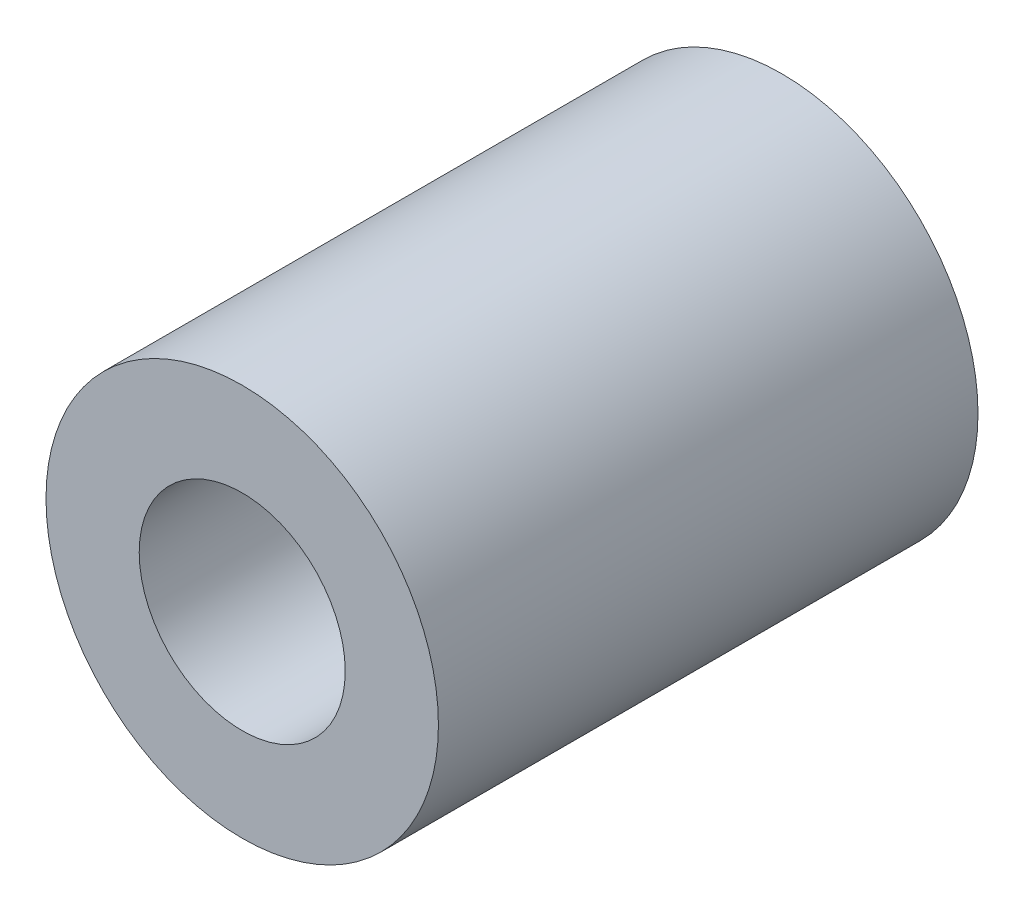
SolidWorks part; units mm, degrees
ref_plane "正面" through (0, 0, 0) normal (0, 0, 1) x (1, 0, 0)
ref_plane "平面" through (0, 0, 0) normal (0, 1, 0) x (1, 0, 0)
ref_plane "右側面" through (0, 0, 0) normal (1, 0, 0) x (0, 0, -1)
sketch "ｽｹｯﾁ1" plane through (0, 0, 0) normal (0, 0, 1) x (1, 0, 0)
  circle A0 centre (0, 0) radius 4
  circle A1 centre (0, 0) radius 2.1
  dimension "D1" = 8
  dimension "D2" = 4.2
extrude "ﾎﾞｽ - 押し出し1" add sketch "ｽｹｯﾁ1" along normal blind 11
